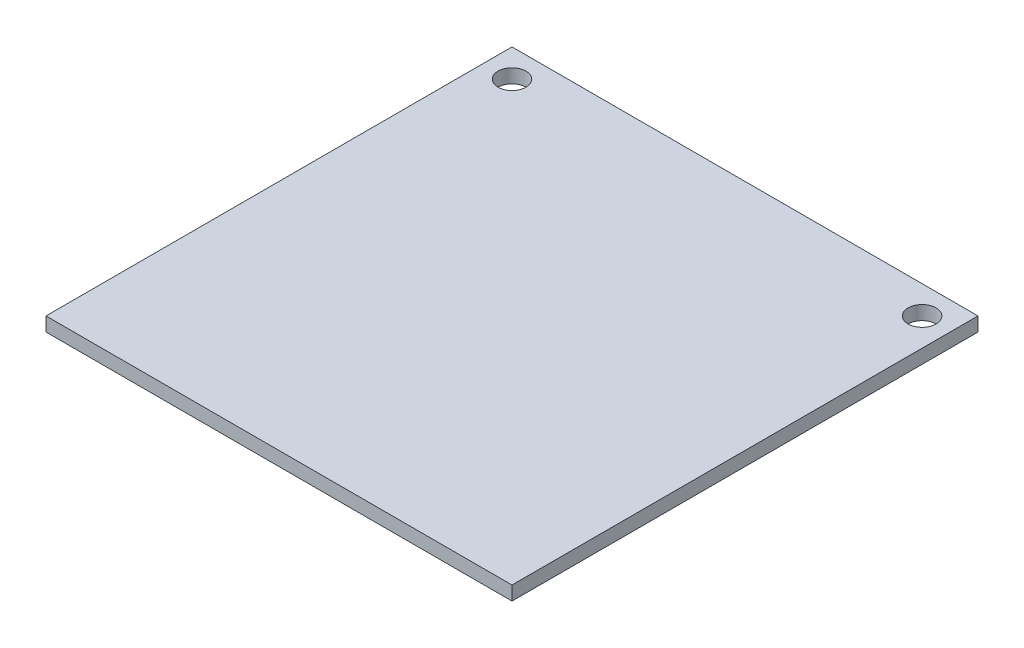
SolidWorks part; units mm, degrees
ref_plane "Front Plane" through (0, 0, 0) normal (0, 0, 1) x (1, 0, 0)
ref_plane "Top Plane" through (0, 0, 0) normal (0, 1, 0) x (1, 0, 0)
ref_plane "Right Plane" through (0, 0, 0) normal (1, 0, 0) x (0, 0, -1)
sketch "Sketch1" plane through (0, 0, 0) normal (0, 1, 0) x (1, 0, 0)
  line L1 (0, 0) -> (50, 0)
  line L2 (0, 0) -> (0, 50)
  line L3 (0, 50) -> (50, 50)
  line L4 (50, 0) -> (50, 50)
  circle A0 centre (47, 47) radius 1.5
  circle A1 centre (3, 47) radius 1.5
  dimension "D1" = 3
  dimension "D2" = 3
  dimension "D3" = 3
  dimension "D4" = 3
  dimension "D5" = 50
  dimension "D6" = 50
extrude "Boss-Extrude1" add sketch "Sketch1" along normal blind 1.5
